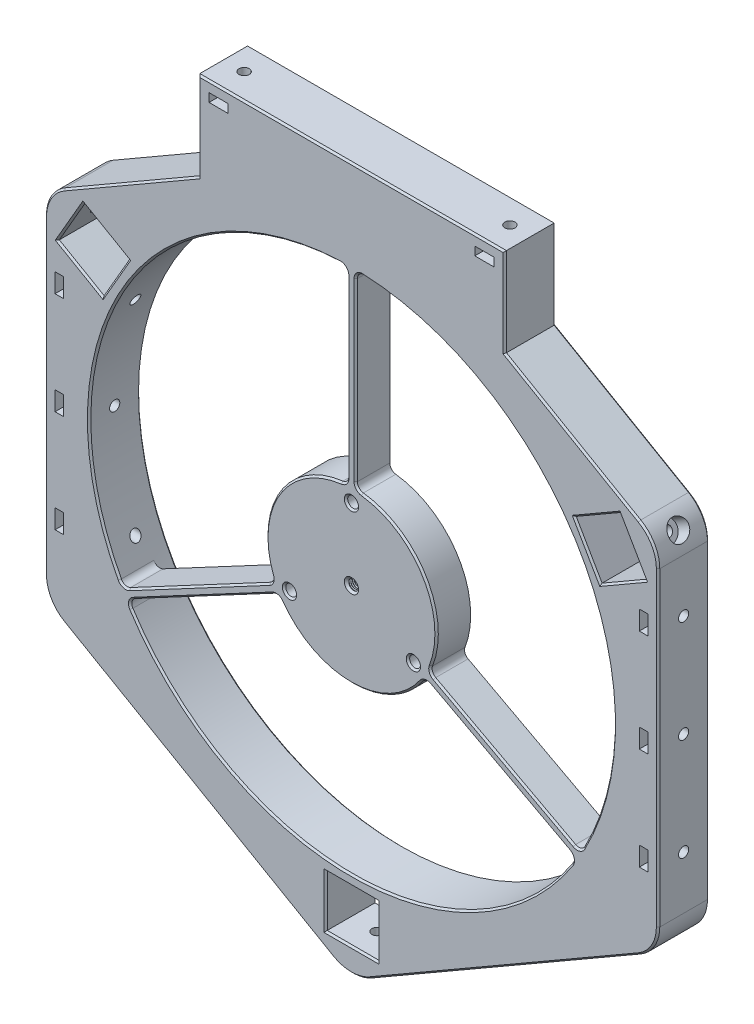
SolidWorks part; units mm, degrees
ref_plane "Top Plane" through (0, 0, 0) normal (0, 0, 1) x (1, 0, 0)
ref_plane "Front Plane" through (0, 0, 0) normal (0, 1, 0) x (1, 0, 0)
ref_plane "Right Plane" through (0, 0, 0) normal (1, 0, 0) x (0, 0, -1)
sketch "Sketch1" plane through (0, 0, 0) normal (0, 0, 1) x (1, 0, 0)
  line L0 (0, 0) -> (0, 121.7219) construction
  line L1 (0, 0) -> (107.9732, 62.3384) construction
  line L2 (0, 0) -> (110.8259, -63.9854) construction
  line L3 (0, 0) -> (0, -117.8434) construction
  line L4 (0, 0) -> (-109.5488, -63.248) construction
  line L5 (0, 0) -> (-114.2494, 65.9619) construction
  line L6 (45, 77.9423) -> (90, 51.9615)
  line L7 (90, 51.9615) -> (90, -51.9615)
  line L8 (90, -51.9615) -> (0, -103.923)
  line L9 (0, -103.923) -> (-90, -51.9615)
  line L10 (-90, -51.9615) -> (-90, 51.9615)
  line L11 (-90, 51.9615) -> (-45, 77.9423)
  line L12 (-45, 77.9423) -> (-45, 103.923)
  line L13 (-45, 103.923) -> (45, 103.923)
  line L14 (45, 77.9423) -> (45, 103.923)
  circle A0 centre (0, 0) radius 77
  circle A1 centre (0, 0) radius 103.923 construction
  dimension "D1" = 154
  dimension "D4" = 180
  dimension "D2" = 60
  dimension "D3" = 60
  dimension "D5" = 180
  dimension "D6" = 180
  dimension "D7" = 90
extrude "Boss-Extrude1" add sketch "Sketch1" along normal blind 15
sketch "Sketch2" plane through (0, 0, 15) normal (0, 0, 1) x (1, 0, 0)
  line L0 (0, 0) -> (0, -120.5827) construction
  line L1 (-7.6, -80) -> (7.6, -80)
  line L2 (-7.6, -80) -> (-7.6, -95.2)
  line L3 (-7.6, -95.2) -> (7.6, -95.2)
  line L4 (7.6, -80) -> (7.6, -95.2)
  line L5 (-7.6, -80) -> (7.6, -95.2) construction
  line L6 (-7.6, -95.2) -> (7.6, -80) construction
  line L7 (-65.482, 46.5818) -> (-73.082, 33.4182)
  line L8 (-65.482, 46.5818) -> (-78.6456, 54.1818)
  line L9 (-78.6456, 54.1818) -> (-86.2456, 41.0182)
  line L10 (-73.082, 33.4182) -> (-86.2456, 41.0182)
  line L11 (-65.482, 46.5818) -> (-86.2456, 41.0182) construction
  line L12 (-78.6456, 54.1818) -> (-73.082, 33.4182) construction
  line L13 (73.082, 33.4182) -> (65.482, 46.5818)
  line L14 (73.082, 33.4182) -> (86.2456, 41.0182)
  line L15 (86.2456, 41.0182) -> (78.6456, 54.1818)
  line L16 (65.482, 46.5818) -> (78.6456, 54.1818)
  line L17 (73.082, 33.4182) -> (78.6456, 54.1818) construction
  line L18 (86.2456, 41.0182) -> (65.482, 46.5818) construction
  point P0 (0, -87.6)
  point P8 (-75.8638, 43.8)
  point P15 (75.8638, 43.8)
  point P20 (0, 0)
  dimension "D1" = 80
  dimension "D2" = 15.2
  dimension "D3" = 15.2
  dimension "D4" = 3
extrude "Cut-Extrude1" cut sketch "Sketch2" against normal through all
fillet "Fillet1" radius 11.11 5 edges at (-90, -51.9615, 7.5) (-90, 51.9615, 7.5) (90, 51.9615, 7.5) (90, -51.9615, 7.5) (0, -103.923, 7.5)
ref_plane "Plane1" through (0, 0, 0) normal (-0.866, 0.5, 0) x (0, 0, -1)
sketch "Sketch9" plane through (-82.4456, 47.6, 0) normal (0.866, -0.5, 0) x (0, 0, -1)
  line L0 (0, 0) -> (-36.7336, 0) construction
  line L2 (-15, 7.6) -> (-15, -7.6) construction
  circle A0 centre (-7.5, 0) radius 1.5
  dimension "D1" = 3
  dimension "D2" = 7.5
extrude "Cut-Extrude6" cut sketch "Sketch9" against normal blind 3
sketch "Sketch10" plane through (-85.0437, 49.1, 0) normal (0.866, -0.5, 0) x (0, 0, -1)
  circle A0 centre (-7.5, 0) radius 3
  dimension "D1" = 6
extrude "Cut-Extrude7" cut sketch "Sketch10" against normal through all
pattern_circular "CirPattern2" count 3 over 360 about axis through (0, 0, 0) along (0, 0, 1) of "Cut-Extrude6", "Cut-Extrude7"
sketch "Sketch15" plane through (0, 0, 15) normal (0, 0, 1) x (1, 0, 0)
  line L0 (0, 0) -> (0, 105.3943) construction
  line L1 (-1.25, 76.9899) -> (-1.25, 21.4687)
  line L2 (1.25, 76.9899) -> (1.25, 21.4687)
  line L7 (-78.89, -45.5472) -> (0, -3.5) construction
  line L8 (0, -3.5) -> (78.89, -45.5472) construction
  line L9 (-67.0668, -37.8291) -> (-22.6224, -14.1409)
  line L10 (-65.8024, -39.9881) -> (-21.4465, -16.3471)
  line L11 (21.4465, -16.3471) -> (65.8024, -39.9881)
  line L12 (22.6224, -14.1409) -> (67.0668, -37.8291)
  circle A3 centre (0, 0) radius 77 construction
  arc A11 (-1.25, 21.4687) -> (-22.6224, -14.1409) centre (0, -3.5) ccw
  arc A13 (1.25, 76.9899) -> (-1.25, 76.9899) centre (0, 0) ccw
  circle A14 centre (0, 0) radius 77
  arc A15 (-67.0668, -37.8291) -> (-65.8024, -39.9881) centre (0, 0) ccw
  arc A16 (65.8024, -39.9881) -> (67.0668, -37.8291) centre (0, 0) ccw
  arc A17 (-21.4465, -16.3471) -> (21.4465, -16.3471) centre (0, -3.5) ccw
  arc A18 (22.6224, -14.1409) -> (1.25, 21.4687) centre (0, -3.5) ccw
  dimension "D4" = 3.5
  dimension "D5" = 50
  dimension "D6" = 0
  dimension "D2" = 2.5
  dimension "D1" = 2.5
  dimension "D3" = 2.5
extrude "Boss-Extrude2" add sketch "Sketch15" against normal blind 10
fillet "Fillet2" radius 2 12 edges at (1.25, 76.9899, 10) (-1.25, 76.9899, 10) (22.6224, -14.1409, 10) (21.4465, -16.3471, 10) (-1.25, 21.4687, 10) (1.25, 21.4687, 10) (65.8024, -39.9881, 10) (67.0668, -37.8291, 10) (-21.4465, -16.3471, 10) (-22.6224, -14.1409, 10) (-67.0668, -37.8291, 10) (-65.8024, -39.9881, 10)
sketch "Sketch19" plane through (0, 103.923, 0) normal (0, 1, 0) x (1, 0, 0)
  line L0 (-52.753, -7.5) -> (49.8223, -7.5) construction
  line L1 (0, 0) -> (0, -29.5407) construction
  circle A0 centre (-39, -7.5) radius 1.5
  circle A1 centre (39, -7.5) radius 1.5
  dimension "D2" = 3
  dimension "D1" = 7.5
  dimension "D3" = 39
  dimension "D4" = 39
extrude "Cut-Extrude14" cut sketch "Sketch19" against normal blind 30
sketch "Sketch16" plane through (0, 0, 15) normal (0, 0, 1) x (1, 0, 0)
  circle A0 centre (0, -3.5) radius 1.55
  dimension "D1" = 3.1
extrude "Cut-Extrude11" cut sketch "Sketch16" against normal through all
sketch "Sketch30" plane through (0, 0, 0) normal (0, 0, -1) x (-1, 0, 0)
  line L0 (-45, 103.923) -> (45, 103.923) construction
  line L1 (-41.8, 100.923) -> (-36.2, 100.923)
  line L3 (-41.8, 98.423) -> (-36.2, 98.423)
  line L5 (-39, 106.0391) -> (-39, 97.7499) construction
  line L8 (0, 0) -> (0, 119.5709) construction
  line L9 (-41.8, 100.923) -> (-41.8, 98.423)
  line L10 (-36.2, 100.923) -> (-36.2, 98.423)
  line L11 (36.2, 100.923) -> (36.2, 98.423)
  line L12 (41.8, 100.923) -> (41.8, 98.423)
  line L13 (41.8, 98.423) -> (36.2, 98.423)
  line L14 (41.8, 100.923) -> (36.2, 100.923)
  line L15 (-37.5, 73.923) -> (-37.5, 103.923) construction
  line L16 (-40.5, 103.923) -> (-40.5, 73.923) construction
  point P12 (-39, 100.923)
  dimension "D1" = 5.6
  dimension "D2" = 2.5
  dimension "D3" = 3
extrude "Cut-Extrude16" cut sketch "Sketch30" against normal through all
sketch "Sketch23" plane through (0, 0, 15) normal (0, 0, 1) x (1, 0, 0)
  circle A2 centre (0, -3.5) radius 1.55
  circle A4 centre (0, -3.5) radius 1.55
  dimension "D1" = 0
curve "Helix/Spiral1" pitch 0.5 height 10 turns 20
sketch "Sketch25" plane through (0, 0, 0) normal (1, 0, 0) x (0, 0, -1)
  line L4 (-15, -1.95) -> (-14.65, -1.95)
  line L5 (-15, -45.5472) -> (-15, 45.5472) construction
  line L6 (-14.65, -1.95) -> (-14.825, -2.2531)
  line L7 (-14.825, -2.2531) -> (-15, -1.95)
  line L8 (-5, -1.95) -> (-15, -1.95) construction
  dimension "D1" = 0.35
sweep "Sweep1" add profiles "Sketch25" path "Helix/Spiral1"
sketch "Sketch29" plane through (0, 0, 0) normal (1, 0, 0) x (0, 0, -1)
  line L0 (-15, -3.5) -> (-15, -1.4)
  line L2 (-15, -45.5472) -> (-15, 45.5472) construction
  line L3 (-15, -1.4) -> (-12.9, -3.5)
  line L4 (-12.9, -3.5) -> (-15, -3.5)
  line L5 (-5, -3.5) -> (-15, -3.5) construction
  dimension "D1" = 2.1
revolve "Cut-Revolve1" cut sketch "Sketch29" angle 360 about axis through (0, -3.5, 0) along (0, 0, 1)
sketch "Sketch18" plane through (0, 0, 15) normal (0, 0, 1) x (1, 0, 0)
  line L0 (0, -3.5) -> (0, 16.5136) construction
  circle A0 centre (0, 17.5) radius 1.6
  point P13 (0, -3.5)
  dimension "D2" = 3.2
  dimension "D1" = 21
extrude "Cut-Extrude13" cut sketch "Sketch18" against normal through all
pattern_circular "CirPattern3" count 3 over 360 about axis through (0, -3.5, 0) along (0, 0, 1) of "Cut-Extrude13"
sketch "Sketch31" plane through (90, 0, 0) normal (1, 0, 0) x (0, 0, -1)
  line L0 (-7.5, 30) -> (-7.5, -30) construction
  line L1 (0, 0) -> (-19.4986, 0) construction
  circle A0 centre (-7.5, 30) radius 1.5
  circle A1 centre (-7.5, -30) radius 1.5
  circle A2 centre (-7.5, 0) radius 1.5
  dimension "D2" = 30
  dimension "D3" = 30
  dimension "D4" = 3
  dimension "D1" = 7.5
extrude "Cut-Extrude17" cut sketch "Sketch31" against normal blind 20
mirror "Mirror1" about plane through (0, 0, 0) normal (1, 0, 0) of "Cut-Extrude17"
sketch "Sketch32" plane through (0, 0, 15) normal (0, 0, 1) x (1, 0, 0)
  line L0 (-94.375, 30) -> (-80.783, 30) construction
  line L1 (-70.262, 31.5) -> (-90, 31.5) construction
  line L2 (-87, 32.8) -> (-84.5, 32.8)
  line L3 (-87, 32.8) -> (-87, 27.2)
  line L4 (-87, 27.2) -> (-84.5, 27.2)
  line L5 (-84.5, 32.8) -> (-84.5, 27.2)
  line L6 (-90, 28.5) -> (-71.5315, 28.5) construction
  line L8 (-92.205, 0) -> (-82.0486, 0) construction
  line L9 (8.25, 0) -> (-8.25, 0) construction
  line L10 (-87, 2.8) -> (-84.5, 2.8)
  line L11 (-87, 2.8) -> (-87, -2.8)
  line L12 (-87, -2.8) -> (-84.5, -2.8)
  line L13 (-84.5, 2.8) -> (-84.5, -2.8)
  line L14 (-94.375, -30) -> (-80.783, -30) construction
  line L15 (-84.5, -32.8) -> (-84.5, -27.2)
  line L16 (-87, -27.2) -> (-84.5, -27.2)
  line L17 (-87, -32.8) -> (-87, -27.2)
  line L18 (-87, -32.8) -> (-84.5, -32.8)
  line L19 (0, -8.25) -> (0, 8.25) construction
  line L20 (94.375, -30) -> (80.783, -30) construction
  line L21 (92.205, 0) -> (82.0486, 0) construction
  line L22 (94.375, 30) -> (80.783, 30) construction
  line L23 (87, -32.8) -> (84.5, -32.8)
  line L24 (87, -32.8) -> (87, -27.2)
  line L25 (87, -27.2) -> (84.5, -27.2)
  line L26 (84.5, -32.8) -> (84.5, -27.2)
  line L27 (84.5, 2.8) -> (84.5, -2.8)
  line L28 (87, -2.8) -> (84.5, -2.8)
  line L29 (87, 2.8) -> (87, -2.8)
  line L30 (87, 2.8) -> (84.5, 2.8)
  line L31 (84.5, 32.8) -> (84.5, 27.2)
  line L32 (87, 27.2) -> (84.5, 27.2)
  line L33 (87, 32.8) -> (87, 27.2)
  line L34 (87, 32.8) -> (84.5, 32.8)
  line L35 (-90, 45.5472) -> (-90, -45.5472) construction
  dimension "D1" = 5.6
  dimension "D2" = 2.5
  dimension "D3" = 3
  dimension "D4" = 5.6
  dimension "D5" = 2.5
  dimension "D6" = 3
extrude "Cut-Extrude18" cut sketch "Sketch32" against normal through all
chamfer "Chamfer1" distance 0.5 angle 45 112 edges at (77, 0, 0) (0, -102.2043, 0) (45, -77.9423, 0) (88.5115, -51.1022, 0) (90, 0, 0) (88.5115, 51.1022, 0) (64.7225, 66.5555, 0) (-64.7225, 66.5555, 0) (-88.5115, 51.1022, 0) (-90, 0, 0) (-88.5115, -51.1022, 0) (-45, -77.9423, 0) (82.4456, 47.6, 0) (79.6638, 37.2182, 0) (69.282, 40, 0) (72.0638, 50.3818, 0) (-82.4456, 47.6, 0) (-72.0638, 50.3818, 0) (-69.282, 40, 0) (-79.6638, 37.2182, 0) (0, -95.2, 0) (-7.6, -87.6, 0) (0, -80, 0) (7.6, -87.6, 0) (-21.6587, -17.0303, 15) (-43.4872, -28.0945, 15) (-64.904, -40.2423, 15) (0, -77, 15) (64.904, -40.2423, 15) (43.4872, -28.0945, 15) (21.6587, -17.0303, 15) (0, -28.5, 15) (-88.5115, 51.1022, 15) (-64.7225, 66.5555, 15) (64.7225, 66.5555, 15) (88.5115, 51.1022, 15) (90, 0, 15) (88.5115, -51.1022, 15) (45, -77.9423, 15) (0, -102.2043, 15) (-45, -77.9423, 15) (-88.5115, -51.1022, 15) (-90, 0, 15) (79.6638, 37.2182, 15) (82.4456, 47.6, 15) (72.0638, 50.3818, 15) (69.282, 40, 15) (-72.0638, 50.3818, 15) (-82.4456, 47.6, 15) (-79.6638, 37.2182, 15) (-69.282, 40, 15) (-7.6, -87.6, 15) (0, -95.2, 15) (7.6, -87.6, 15) (0, -80, 15) (1.8668, 76.3741, 15) (1.25, 49.1166, 15) (1.7531, 21.9773, 15) (21.4356, 9.3653, 15) (23.3078, -13.9362, 15) (44.7814, -25.9513, 15) (66.8467, -37.0463, 15) (66.8237, 38.2569, 15) (-66.8467, -37.0463, 15) (-44.7814, -25.9513, 15) (-23.3078, -13.9362, 15) (-21.4356, 9.3653, 15) (-1.7531, 21.9773, 15) (-1.25, 49.1166, 15) (-1.8668, 76.3741, 15) (-66.8237, 38.2569, 15) (1.6, 17.5, 15) (45, 90.9327, 0) (0, 103.923, 0) (-45, 90.9327, 0) (-45, 90.9327, 15) (0, 103.923, 15) (45, 90.9327, 15) (-36.2, 99.673, 0) (-39, 98.423, 0) (-41.8, 99.673, 0) (-39, 100.923, 0) (39, 98.423, 0) (36.2, 99.673, 0) (39, 100.923, 0) (41.8, 99.673, 0) (-85.75, 32.8, 0) (-84.5, 30, 0) (-85.75, 27.2, 0) (-87, 30, 0) (-85.75, 2.8, 0) (-84.5, 0, 0) (-85.75, -2.8, 0) (-87, 0, 0) (-87, -30, 0) (-85.75, -27.2, 0) (-84.5, -30, 0) (-85.75, -32.8, 0) (85.75, -32.8, 0) (84.5, -30, 0) (85.75, -27.2, 0) (87, -30, 0) (87, 0, 0) (85.75, -2.8, 0) (84.5, 0, 0) (85.75, 2.8, 0) (87, 30, 0) (85.75, 27.2, 0) (84.5, 30, 0) (85.75, 32.8, 0) (17.3865, -15.3856, 15) (-18.9865, -12.6144, 15)
